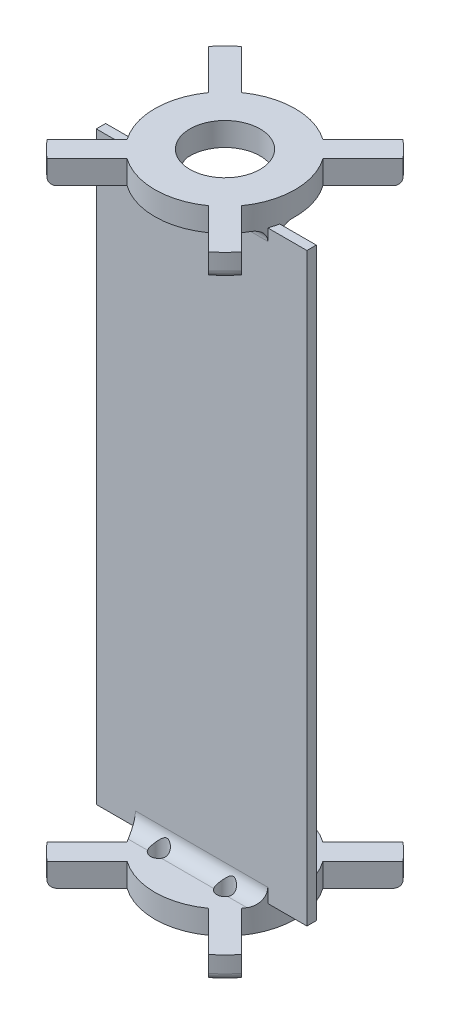
SolidWorks part; units mm, degrees
ref_plane "Front Plane" through (0, 0, 0) normal (0, 0, 1) x (1, 0, 0)
ref_plane "Top Plane" through (0, 0, 0) normal (0, 1, 0) x (1, 0, 0)
ref_plane "Right Plane" through (0, 0, 0) normal (1, 0, 0) x (0, 0, -1)
sketch "Sketch1" plane through (0, 0, 0) normal (0, 1, 0) x (1, 0, 0)
  line L0 (-38.8166, 0) -> (-27, 0) construction
  line L1 (0, 33.4027) -> (0, -15) construction
  line L2 (-19.0919, 19.0919) -> (0, 0) construction
  line L3 (-17.2421, 20.7776) -> (-8.6905, 12.226)
  line L4 (-20.7776, 17.2421) -> (-12.226, 8.6905)
  line L5 (20.7776, 17.2421) -> (12.226, 8.6905)
  line L6 (17.2421, 20.7776) -> (8.6905, 12.226)
  line L7 (17.2421, -20.7776) -> (8.6905, -12.226)
  line L8 (20.7776, -17.2421) -> (12.226, -8.6905)
  line L9 (-20.7776, -17.2421) -> (-12.226, -8.6905)
  line L10 (-17.2421, -20.7776) -> (-8.6905, -12.226)
  line L11 (0, -27) -> (0, -35.1903) construction
  line L12 (-15, 0) -> (40.6042, 0) construction
  line L13 (-19.0919, 19.0919) -> (-36.0075, 36.0075) construction
  arc A0 (-17.2421, 20.7776) -> (-20.7776, 17.2421) centre (0, 0) ccw construction
  arc A1 (-12.226, 8.6905) -> (-12.226, -8.6905) centre (0, 0) ccw
  arc A2 (-17.2421, 20.7776) -> (-20.7776, 17.2421) centre (0, 0) ccw
  arc A3 (20.7776, 17.2421) -> (17.2421, 20.7776) centre (0, 0) ccw construction
  arc A4 (20.7776, 17.2421) -> (17.2421, 20.7776) centre (0, 0) ccw
  arc A5 (17.2421, -20.7776) -> (20.7776, -17.2421) centre (0, 0) ccw construction
  arc A6 (17.2421, -20.7776) -> (20.7776, -17.2421) centre (0, 0) ccw
  arc A7 (-20.7776, -17.2421) -> (-17.2421, -20.7776) centre (0, 0) ccw construction
  arc A8 (-20.7776, -17.2421) -> (-17.2421, -20.7776) centre (0, 0) ccw
  arc A9 (8.6905, 12.226) -> (-8.6905, 12.226) centre (0, 0) ccw
  arc A10 (12.226, -8.6905) -> (12.226, 8.6905) centre (0, 0) ccw
  arc A11 (-8.6905, -12.226) -> (8.6905, -12.226) centre (0, 0) ccw
  circle A12 centre (-7.0711, 7.0711) radius 1.75
  circle A13 centre (7.0711, 7.0711) radius 1.75
  circle A14 centre (7.0711, -7.0711) radius 1.75
  circle A15 centre (-7.0711, -7.0711) radius 1.75
  point P29 (0, 0)
  point P40 (0, 0)
  dimension "D1" = 54
  dimension "D2" = 30
  dimension "D5" = 3.5
  dimension "D3" = 5
  dimension "D6" = 10
  dimension "D4" = 4
  dimension "D7" = 4
extrude "Boss-Extrude1" add sketch "Sketch1" along normal blind 5
sketch "Sketch2" plane through (0, 5, 0) normal (0, 1, 0) x (1, 0, 0)
  line L0 (-26.5708, 0) -> (29.8317, 0) construction
  line L1 (0, 20.3293) -> (0, -19.9982) construction
  line L3 (-22.5, -3) -> (22.5, -3)
  line L4 (-22.5, -3) -> (-22.5, -5)
  line L5 (-22.5, -5) -> (22.5, -5)
  line L6 (22.5, -3) -> (22.5, -5)
  line L7 (-22.5, -3) -> (22.5, -5) construction
  line L8 (-22.5, -5) -> (22.5, -3) construction
  point P5 (0, -4)
  dimension "D1" = 3
  dimension "D2" = 2
  dimension "D3" = 45
extrude "Boss-Extrude2" add sketch "Sketch2" along normal blind 125
fillet "Fillet1" radius 3 2 edges at (0, 5, 5) (0, 5, 3)
sketch "Sketch3" plane through (0, 130, 0) normal (0, 1, 0) x (1, 0, 0)
  line L0 (0, 23.9917) -> (0, -28.8781) construction
  line L1 (-30.3748, 0) -> (15, 0) construction
  line L2 (-17.2421, 20.7776) -> (-8.6905, 12.226)
  line L3 (-20.7776, 17.2421) -> (-12.226, 8.6905)
  line L4 (20.7776, 17.2421) -> (12.226, 8.6905)
  line L5 (17.2421, 20.7776) -> (8.6905, 12.226)
  line L6 (17.2421, -20.7776) -> (8.6905, -12.226)
  line L7 (20.7776, -17.2421) -> (12.226, -8.6905)
  line L8 (-20.7776, -17.2421) -> (-12.226, -8.6905)
  line L9 (-17.2421, -20.7776) -> (-8.6905, -12.226)
  line L10 (27, 0) -> (30.0226, 0) construction
  circle A0 centre (0, 0) radius 7.5
  arc A1 (-12.226, 8.6905) -> (-12.226, -8.6905) centre (0, 0) ccw
  arc A2 (-20.7776, -17.2421) -> (-17.2421, -20.7776) centre (0, 0) ccw
  arc A3 (-20.7776, -17.2421) -> (-17.2421, -20.7776) centre (0, 0) ccw
  arc A4 (-20.7776, -17.2421) -> (-17.2421, -20.7776) centre (0, 0) ccw
  arc A5 (-20.7776, -17.2421) -> (-17.2421, -20.7776) centre (0, 0) ccw
  arc A6 (8.6905, 12.226) -> (-8.6905, 12.226) centre (0, 0) ccw
  arc A7 (12.226, -8.6905) -> (12.226, 8.6905) centre (0, 0) ccw
  arc A8 (-8.6905, -12.226) -> (8.6905, -12.226) centre (0, 0) ccw
  arc A9 (-17.2421, 20.7776) -> (-20.7776, 17.2421) centre (0, 0) ccw
  arc A10 (-17.2421, 20.7776) -> (-20.7776, 17.2421) centre (0, 0) ccw
  arc A11 (-17.2421, 20.7776) -> (-20.7776, 17.2421) centre (0, 0) ccw
  arc A12 (-17.2421, 20.7776) -> (-20.7776, 17.2421) centre (0, 0) ccw
  arc A13 (20.7776, 17.2421) -> (17.2421, 20.7776) centre (0, 0) ccw
  arc A14 (20.7776, 17.2421) -> (17.2421, 20.7776) centre (0, 0) ccw
  arc A15 (20.7776, 17.2421) -> (17.2421, 20.7776) centre (0, 0) ccw
  arc A16 (20.7776, 17.2421) -> (17.2421, 20.7776) centre (0, 0) ccw
  arc A17 (17.2421, -20.7776) -> (20.7776, -17.2421) centre (0, 0) ccw
  arc A18 (17.2421, -20.7776) -> (20.7776, -17.2421) centre (0, 0) ccw
  arc A19 (17.2421, -20.7776) -> (20.7776, -17.2421) centre (0, 0) ccw
  arc A20 (17.2421, -20.7776) -> (20.7776, -17.2421) centre (0, 0) ccw
  point P35 (0, 0)
  line M3 (22.5, -3) -> (-22.5, -3)
  line M5 (-22.5, -5) -> (22.5, -5)
  dimension "D1" = 15
  dimension "D3" = 4
extrude "Boss-Extrude3" add sketch "Sketch3" along normal blind 5 contours L4 A13 L5 A6 L2 A9 L3 A1 A0 A7 M3 | L6 A17 L7 A7 A0 A1 L8 A2 L9 A8 M5 | A1 A0 M3 M5 | A7 A0 M5 M3 region at (0, 130, -8.5421) region at (-10.369, 130, 4.0148) region at (0, 130, 11.5592) region at (10.369, 130, 4.0148)
fillet "Fillet2" radius 2.5 4 edges at (9.8662, 130, 5) (-9.8662, 130, 5) (10.7854, 130, 3) (-10.7854, 130, 3)
fillet "Fillet3" radius 1.5 8 edges at (19.0919, 130, 19.0919) (-19.0919, 130, 19.0919) (-19.0919, 130, -19.0919) (19.0919, 130, -19.0919) (-19.0919, 0, 19.0919) (19.0919, 0, 19.0919) (19.0919, 0, -19.0919) (-19.0919, 0, -19.0919)
